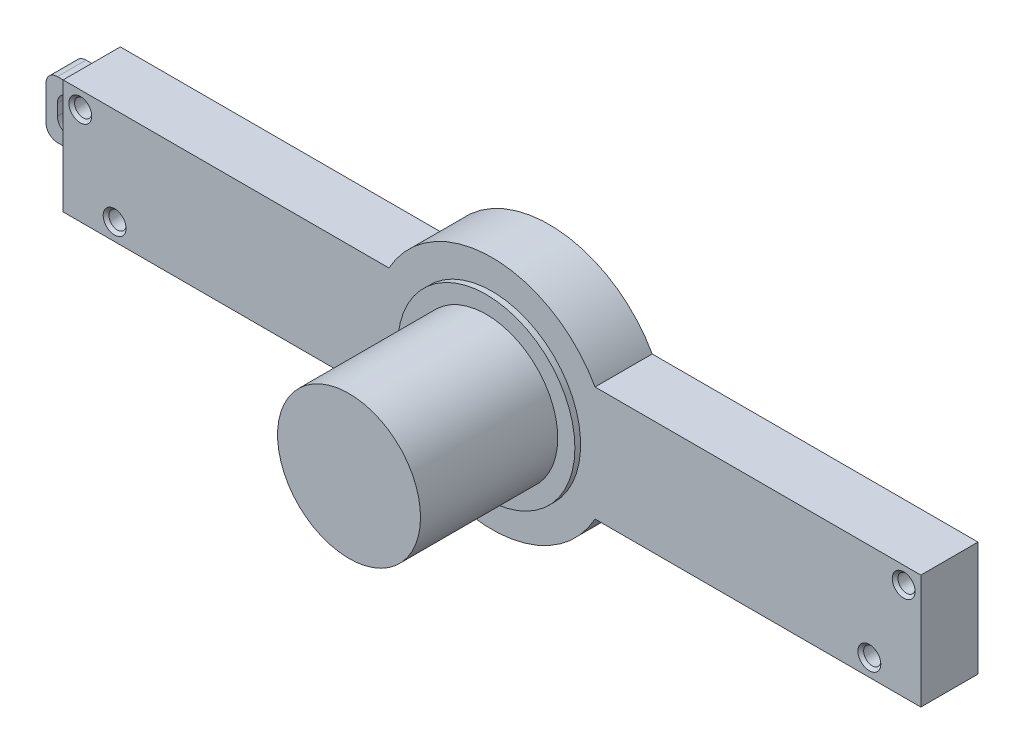
SolidWorks part; units mm, degrees
ref_plane "Płaszczyzna przednia" through (0, 0, 0) normal (0, 0, 1) x (1, 0, 0)
ref_plane "Płaszczyzna górna" through (0, 0, 0) normal (0, 1, 0) x (1, 0, 0)
ref_plane "Płaszczyzna prawa" through (0, 0, 0) normal (1, 0, 0) x (0, 0, -1)
sketch "Szkic1" plane through (0, 0, 0) normal (0, 0, 1) x (1, 0, 0)
  line L1 (-75, -10) -> (75, -10)
  line L2 (-75, -10) -> (-75, 10)
  line L3 (-75, 10) -> (75, 10)
  line L4 (75, -10) -> (75, 10)
  line L5 (-75, -10) -> (75, 10) construction
  line L6 (-75, 10) -> (75, -10) construction
  point P0 (0, 0)
  dimension "D1" = 150
  dimension "D2" = 20
extrude "Dodanie-wyciągnięcie1" add sketch "Szkic1" along normal blind 10
sketch "Szkic2" plane through (0, 0, 10) normal (0, 0, 1) x (1, 0, 0)
  circle A0 centre (0, 0) radius 20.6112
extrude "Dodanie-wyciągnięcie2" add sketch "Szkic2" against normal blind 10
sketch "Szkic3" plane through (0, 0, 10) normal (0, 0, 1) x (1, 0, 0)
  circle A0 centre (0, 0) radius 12.5
  dimension "D1" = 25
extrude "Dodanie-wyciągnięcie5" add sketch "Szkic3" along normal blind 25 contours A0
sketch "Szkic8" plane through (0, 0, 10) normal (0, 0, 1) x (1, 0, 0)
  circle A0 centre (0, 0) radius 15.5
  dimension "D1" = 31
extrude "Dodanie-wyciągnięcie6" add sketch "Szkic8" along normal blind 1
sketch "Szkic9" plane through (0, 0, 0) normal (0, 0, -1) x (-1, 0, 0)
  line L0 (-75, -10) -> (-75, 10) construction
  line L1 (-75, 10) -> (-18.0228, 10) construction
  line L2 (-18.0228, -10) -> (-75, -10) construction
  line L3 (0, 19.25) -> (0, -19.25) construction
  circle A0 centre (-72, 7) radius 1.5
  circle A1 centre (-66, -7) radius 1.5
  circle A2 centre (66, -7) radius 1.5
  circle A3 centre (72, 7) radius 1.5
  dimension "D1" = 3
  dimension "D2" = 3
  dimension "D3" = 3
  dimension "D4" = 3
  dimension "3" = 3
  dimension "9" = 9
extrude "Wytnij-wyciągnięcie1" cut sketch "Szkic9" against normal blind 10
chamfer "Sfazowanie1" distance 0.5 angle 45 4 edges at (-64.5, -7, 10) (-70.5, 7, 10) (64.5, -7, 10) (70.5, 7, 10)
sketch "Szkic10" plane through (-75, 0, 0) normal (-1, 0, 0) x (0, 0, 1)
  line L0 (0, 10) -> (0, -10) construction
  line L1 (5, -5) -> (0, -5)
  line L2 (5, -5) -> (5, 5)
  line L3 (5, 5) -> (0, 5)
  line L4 (0, -5) -> (0, 5)
  line L5 (5, -5) -> (0, 5) construction
  line L6 (5, 5) -> (0, -5) construction
  point P0 (2.5, 0)
  point P7 (0, 0)
  point P8 (0, 0)
  point P9 (0, 0)
  point P10 (0, 0)
  dimension "D1" = 10
  dimension "D2" = 5
extrude "Dodanie-wyciągnięcie7" add sketch "Szkic10" along normal blind 8
sketch "Szkic11" plane through (0, 0, 0) normal (0, 0, -1) x (-1, 0, 0)
  line L0 (75, 10) -> (75, -10) construction
  line L1 (75, -3) -> (81, -3)
  line L2 (75, -3) -> (75, 3)
  line L3 (75, 3) -> (81, 3)
  line L4 (81, -3) -> (81, 3)
  line L5 (75, -3) -> (81, 3) construction
  line L6 (75, 3) -> (81, -3) construction
  line L7 (83, -5) -> (75, -5) construction
  line L8 (83, 5) -> (83, -5) construction
  line L9 (83, 5) -> (75, 5) construction
  point P0 (78, 0)
  dimension "D1" = 0
  dimension "D2" = 2
  dimension "D3" = 2
  dimension "D4" = 2
extrude "Wytnij-wyciągnięcie2" cut sketch "Szkic11" against normal blind 8
fillet "Zaokrąglenie1" radius 2 4 edges at (-83, -5, 2.5) (-83, 5, 2.5) (-81, -3, 2.5) (-81, 3, 2.5)
